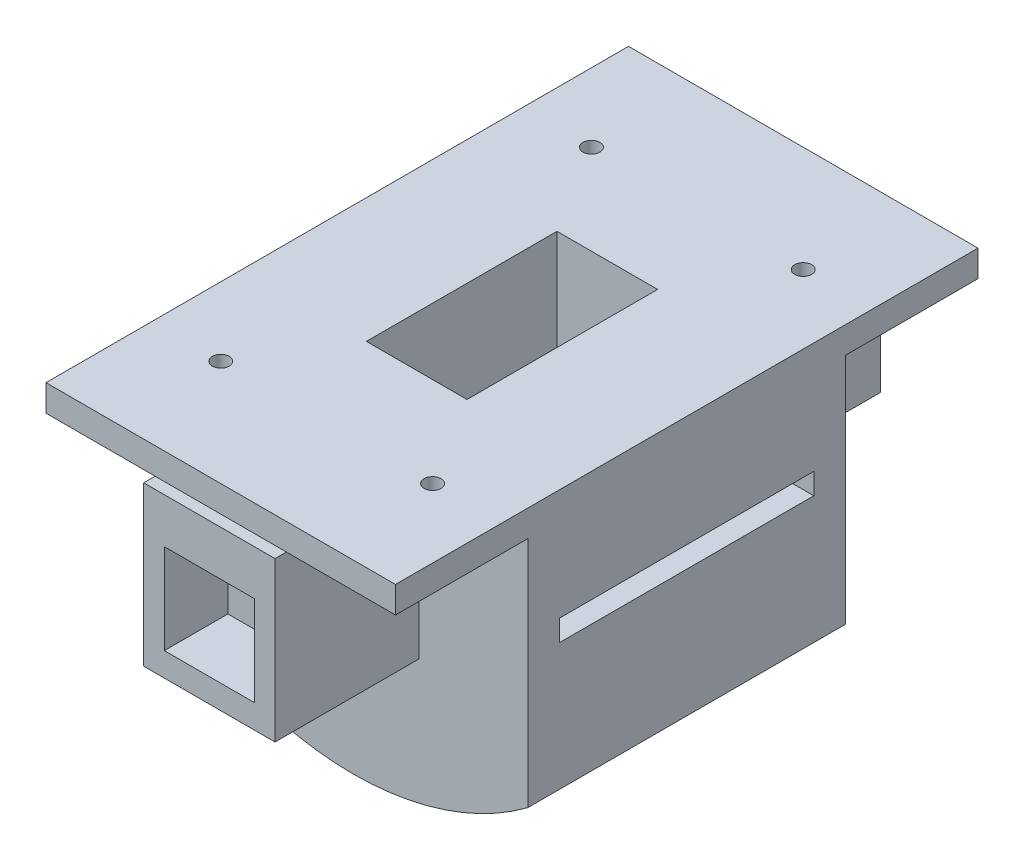
SolidWorks part; units mm, degrees
ref_plane "Front Plane" through (0, 0, 0) normal (0, 0, 1) x (1, 0, 0)
ref_plane "Top Plane" through (0, 0, 0) normal (0, 1, 0) x (1, 0, 0)
ref_plane "Right Plane" through (0, 0, 0) normal (1, 0, 0) x (0, 0, -1)
sketch "Sketch1" plane through (0, 0, 0) normal (0, 0, 1) x (1, 0, 0)
  line L0 (0, 0) -> (0, -42) construction
  line L1 (0, 0) -> (55, 0)
  line L2 (55, 0) -> (-55, 0)
  arc A0 (-55, 0) -> (55, 0) centre (0, 0) ccw
  dimension "D2" = 55
  dimension "D1" = 42
extrude "Boss-Extrude1" add sketch "Sketch1" along normal blind 30 and the other way blind 30 contours L2 A0 L1 region at (0, -23.3427, 0)
sketch "Sketch2" plane through (0, 0, 0) normal (0, 0, 1) x (1, 0, 0)
  line L1 (0, 0) -> (-9.5, 0)
  line L3 (2.8861, -42) -> (-9.5, -42)
  line L4 (-9.5, 0) -> (-9.5, -42)
  line L5 (0, 0) -> (9.5, 0)
  line L7 (2.8861, -42) -> (9.5, -42)
  line L8 (9.5, 0) -> (9.5, -42)
  circle A0 centre (0, 0) radius 42
  dimension "D1" = 84
  dimension "D2" = 9.5
  dimension "D3" = 9.5
  dimension "D4" = 42
extrude "Cut-Extrude1" cut sketch "Sketch2" against normal blind 18 and the other way blind 18 contours L4 A0 L8 L5 L1 | A0 L4 L3 | A0 L3 L7 L8 region at (0, -20.8208, 0) region at (-7.1312, -41.6742, 0) region at (7.1312, -41.6742, 0)
sketch "Sketch3" plane through (0, 0, 30) normal (0, 0, 1) x (1, 0, 0)
  line L0 (0, 0) -> (0, -28.5435) construction
  line L1 (-54.8544, -4) -> (-33, -4)
  line L2 (-54.8544, -4) -> (-54.8544, -49)
  line L3 (-54.8544, -49) -> (-33, -49)
  line L4 (-33, -4) -> (-33, -49)
  line L5 (55, 0) -> (-55, 0) construction
  line L6 (33, -4) -> (33, -49)
  line L7 (54.8544, -49) -> (33, -49)
  line L8 (54.8544, -4) -> (54.8544, -49)
  line L9 (54.8544, -4) -> (33, -4)
  arc A0 (-55, 0) -> (55, 0) centre (0, 0) ccw construction
  dimension "D1" = 4
  dimension "D2" = 33
  dimension "D3" = 45
extrude "Cut-Extrude2" cut sketch "Sketch3" against normal through all
sketch "Sketch4" plane through (0, 0, 0) normal (0, 1, 0) x (1, 0, 0)
  line L0 (55, 30) -> (-55, 30) construction
  line L1 (55, 30) -> (55, -30) construction
  line L2 (0, 0) -> (0, 55.9923) construction
  line L3 (0, 0) -> (36.0907, 0) construction
  circle A0 centre (45, 20) radius 1.6
  circle A1 centre (45, -20) radius 1.6
  circle A2 centre (-45, -20) radius 1.6
  circle A3 centre (-45, 20) radius 1.6
  dimension "D1" = 3.2
  dimension "D2" = 10
  dimension "D3" = 10
extrude "Cut-Extrude3" cut sketch "Sketch4" against normal through all
sketch "Sketch6" plane through (33, 0, 0) normal (1, 0, 0) x (0, 0, -1)
  line L0 (-30, -4) -> (-30, -44) construction
  line L1 (-24, -16) -> (24, -16)
  line L2 (-24, -16) -> (-24, -20)
  line L3 (-24, -20) -> (24, -20)
  line L4 (24, -16) -> (24, -20)
  line L5 (30, -4) -> (30, -44) construction
  line L6 (30, -4) -> (-30, -4) construction
  dimension "D1" = 6
  dimension "D2" = 6
  dimension "D3" = 12
  dimension "D4" = 4
extrude "Cut-Extrude5" cut sketch "Sketch6" against normal blind 22
sketch "Sketch9" plane through (0, 0, 0) normal (0, 1, 0) x (1, 0, 0)
  line L5 (-55, 30) -> (-33, 30)
  line L6 (-55, 30) -> (-55, -30)
  line L7 (-55, -30) -> (-33, -30)
  line L8 (-33, 30) -> (-33, -30)
  line L9 (55, 30) -> (33, 30)
  line L10 (55, 30) -> (55, -30)
  line L11 (55, -30) -> (33, -30)
  line L12 (33, 30) -> (33, -30)
extrude "Cut-Extrude7" cut sketch "Sketch9" against normal through all
sketch "Sketch10" plane through (0, 0, 0) normal (0, 1, 0) x (1, 0, 0)
  line L1 (-33, 30) -> (33, 30)
  line L2 (-33, 30) -> (-33, -30)
  line L3 (-33, -30) -> (33, -30)
  line L4 (33, 30) -> (33, -30)
  line L5 (33, -30) -> (-33, -30)
  line L6 (33, -30) -> (33, -55)
  line L7 (33, -55) -> (-33, -55)
  line L8 (-33, -30) -> (-33, -55)
  line L9 (-33, 30) -> (33, 30)
  line L10 (-33, 30) -> (-33, 55)
  line L11 (-33, 55) -> (33, 55)
  line L12 (33, 30) -> (33, 55)
  line L13 (-9.5, 18) -> (9.5, 18)
  line L14 (-9.5, 18) -> (-9.5, -18)
  line L15 (-9.5, -18) -> (9.5, -18)
  line L16 (9.5, 18) -> (9.5, -18)
  line M3 (-33, 30) -> (-33, -30)
  line M4 (-33, -30) -> (33, -30)
  line M5 (33, -30) -> (33, 30)
  line M6 (33, 30) -> (-33, 30)
  line M7 (9.5, -18) -> (-9.5, -18)
  line M8 (-9.5, -18) -> (-9.5, 18)
  line M9 (-9.5, 18) -> (9.5, 18)
  line M10 (9.5, 18) -> (9.5, -18)
  dimension "D1" = 25
  dimension "D2" = 25
extrude "Boss-Extrude2" add sketch "Sketch10" along normal blind 5 contours L12 L11 L10 M6 | M6 M3 M4 M5 M10 M7 M8 M9 | L8 L7 L6 M4 region at (0, 0, -42.5) region at (0, 0, -29.108) region at (0, 0, 42.5)
sketch "Sketch11" plane through (0, 5, 0) normal (0, 1, 0) x (1, 0, 0)
  line L0 (0, 0) -> (-22.9202, 0) construction
  line L1 (-22.9202, 0) -> (0, 0) construction
  circle A0 centre (-20, 35) radius 1.6
  circle A1 centre (20, 35) radius 1.6
  circle A2 centre (-20, -35) radius 1.6
  circle A3 centre (20, -35) radius 1.6
  dimension "D1" = 3.2
  dimension "D2" = 35
  dimension "D3" = 20
  dimension "D5" = 40
  dimension "D4" = 2
extrude "Cut-Extrude8" cut sketch "Sketch11" against normal through all
sketch "Sketch13" plane through (0, 0, -30) normal (0, 0, -1) x (-1, 0, 0)
  line L0 (33, 0) -> (-33, 0) construction
  line L11 (-18.4, 0) -> (-18.4, 5) construction
  line L12 (-12.4, 0) -> (12.4, 0)
  line L13 (-12.4, 0) -> (-12.4, -30)
  line L14 (-12.4, -30) -> (12.4, -30)
  line L15 (12.4, 0) -> (12.4, -30)
  line L16 (18.4, 5) -> (18.4, 0) construction
  point P0 (0, -17)
  dimension "D5" = 6
  dimension "D6" = 30
  dimension "D7" = 6
extrude "Boss-Extrude3" add sketch "Sketch13" along normal blind 27.15
sketch "Sketch14" plane through (0, 0, -57.15) normal (0, 0, -1) x (-1, 0, 0)
  line L0 (33, -44) -> (33, 0) construction
  line L5 (33, 0) -> (12.4, 0) construction
  line L6 (0, -17) -> (0, 0) construction
  line L7 (-8, -9) -> (8, -9)
  line L8 (-8, -9) -> (-8, -25)
  line L9 (-8, -25) -> (8, -25)
  line L10 (8, -9) -> (8, -25)
  line L11 (-8, -9) -> (8, -25) construction
  line L12 (-8, -25) -> (8, -9) construction
  line L14 (-8.5, -8.5) -> (8.5, -8.5)
  line L15 (-8.5, -8.5) -> (-8.5, -25.5)
  line L16 (-8.5, -25.5) -> (8.5, -25.5)
  line L17 (8.5, -8.5) -> (8.5, -25.5)
  line L18 (-8.5, -8.5) -> (8.5, -25.5) construction
  line L19 (-8.5, -25.5) -> (8.5, -8.5) construction
  point P4 (0, -17)
  dimension "D1" = 16
  dimension "D2" = 9
  dimension "D3" = 16
  dimension "D4" = 25
  dimension "D5" = 17
  dimension "D6" = 0.5
  dimension "D7" = 0.5
extrude "Cut-Extrude9" cut sketch "Sketch14" against normal blind 12 contours L10 L7 L8 L9 | L17 L14 L15 L16 L7 L10 L9 L8 region at (0, -17, -57.15) region at (0, -8.7404, -57.15)
ref_plane "Plane1" through (0, 0, 0) normal (0, 0, -1) x (-1, 0, 0)
mirror "Mirror2" about plane through (0, 0, 0) normal (0, 0, -1) of "Boss-Extrude3"
mirror "Mirror3" about plane through (0, 0, 0) normal (0, 0, -1) of "Cut-Extrude9"
